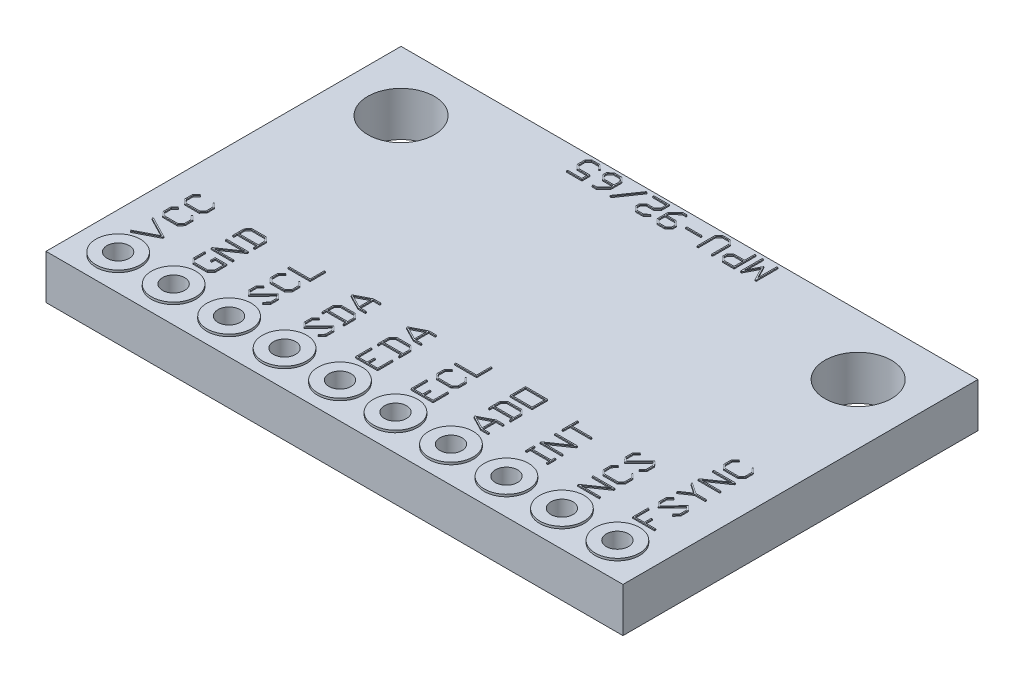
SolidWorks part; units mm, degrees
ref_plane "Alzado" through (0, 0, 0) normal (0, 0, 1) x (1, 0, 0)
ref_plane "Planta" through (0, 0, 0) normal (0, 1, 0) x (1, 0, 0)
ref_plane "Vista lateral" through (0, 0, 0) normal (1, 0, 0) x (0, 0, -1)
sketch "Croquis1" plane through (0, 0, 0) normal (0, 1, 0) x (1, 0, 0)
  line L1 (-13, -8) -> (13, -8)
  line L2 (-13, -8) -> (-13, 8)
  line L3 (-13, 8) -> (13, 8)
  line L4 (13, -8) -> (13, 8)
  line L5 (-13, -8) -> (13, 8) construction
  line L6 (-13, 8) -> (13, -8) construction
  circle A0 centre (-10.3, 5.3) radius 1.5
  circle A1 centre (10.3, 5.3) radius 1.5
  circle A2 centre (11.25, -6.5) radius 0.5
  circle A3 centre (11.25, -6.5) radius 1
  circle A4 centre (8.75, -6.5) radius 0.5
  circle A5 centre (8.75, -6.5) radius 1
  circle A6 centre (6.25, -6.5) radius 0.5
  circle A7 centre (6.25, -6.5) radius 1
  circle A8 centre (3.75, -6.5) radius 0.5
  circle A9 centre (3.75, -6.5) radius 1
  circle A10 centre (1.25, -6.5) radius 0.5
  circle A11 centre (1.25, -6.5) radius 1
  circle A12 centre (-1.25, -6.5) radius 0.5
  circle A13 centre (-1.25, -6.5) radius 1
  circle A14 centre (-3.75, -6.5) radius 0.5
  circle A15 centre (-3.75, -6.5) radius 1
  circle A16 centre (-6.25, -6.5) radius 0.5
  circle A17 centre (-6.25, -6.5) radius 1
  circle A18 centre (-8.75, -6.5) radius 0.5
  circle A19 centre (-8.75, -6.5) radius 1
  circle A20 centre (-11.25, -6.5) radius 0.5
  circle A21 centre (-11.25, -6.5) radius 1
  point P0 (0, 0)
  dimension "D3" = 2.7
  dimension "D7" = 1.5
  dimension "D1" = 26
  dimension "D2" = 16
  dimension "D4" = 2.7
  dimension "D5" = 2.7
  dimension "D6" = 2.7
  dimension "D8" = 1.75
  dimension "D9" = 10
extrude "Saliente-Extruir1" add sketch "Croquis1" against normal blind 2 contours L1 L4 L3 L2 A21 A19 A17 A15 A13 A11 A9 A7 A5 A3 A1 A0 | A3 | A5 | A7 | A9 | A11 | A13 | A15 | A17 | A19 | A21 region at (0, 0, -0.349)
extrude "Cortar-Extruir1" cut sketch "Croquis1<3>" against normal blind 2 contours A20 | A18 | A16 | A14 | A10 | A12 | A8 | A6 | A4 | A2
sketch "Croquis1<3>" plane through (0, 0, 0) normal (0, 1, 0) x (1, 0, 0) same geometry as "Croquis1"
extrude "Saliente-Extruir2" add sketch "Croquis1<4>" along normal blind 0.1 contours A19 A18 | A21 A20 | A17 A16 | A15 A14 | A13 A12 | A11 A10 | A9 A8 | A7 A6 | A5 A4 | A3 A2 region at (10.2783, 0, 6.5) region at (7.7783, 0, 6.5) region at (5.2783, 0, 6.5) region at (2.7783, 0, 6.5) region at (0.2783, 0, 6.5) region at (-2.2217, 0, 6.5) region at (-4.7217, 0, 6.5) region at (-7.2217, 0, 6.5) region at (-9.7217, 0, 6.5) region at (-12.2217, 0, 6.5)
sketch "Croquis1<4>" plane through (0, 0, 0) normal (0, 1, 0) x (1, 0, 0) same geometry as "Croquis1"
sketch "Croquis2" plane through (0, 0, 0) normal (0, 1, 0) x (1, 0, 0)
  line L0 (-10.8805, -5.5708) -> (-10.8805, -2.1435) construction
  line L1 (-8.3805, -5.5708) -> (-8.3805, -2.1435) construction
  line L2 (-5.8805, -5.5708) -> (-5.8805, -2.1435) construction
  line L3 (-3.3805, -5.5708) -> (-3.3805, -2.1435) construction
  line L4 (-0.8805, -5.5708) -> (-0.8805, -2.1435) construction
  line L5 (1.6195, -5.5708) -> (1.6195, -2.1435) construction
  line L6 (4.1195, -5.5708) -> (4.1195, -2.1435) construction
  line L7 (6.6195, -5.5708) -> (6.6195, -2.1435) construction
  line L8 (9.1195, -5.5708) -> (9.1195, -2.1435) construction
  line L9 (11.6195, -5.5708) -> (11.6195, -2.1435) construction
  line L10 (11.6195, -5.5708) -> (11.6195, -0.1979) construction
  circle A0 centre (-11.25, -6.5) radius 1 construction
  text T0 "VCC" font "Txt_IV25" height 1
  text T1 "GND" font "Txt_IV25" height 1
  text T2 "SCL"
  text T3 "SDA"
  text T4 "EDA"
  text T5 "ECL"
  text T6 "ADO"
  text T7 "INT"
  text T8 "NCS"
  text T9 "FSYNC"
  dimension "D1" = 10
extrude "Saliente-Extruir5" add sketch "Croquis2" along normal blind 0.05
sketch "Croquis6" plane through (0, 0, 0) normal (0, 1, 0) x (1, 0, 0)
  line L8 (12.8, -8) -> (12.8, 7.8)
  line L9 (12.8, 7.8) -> (-13, 7.8)
  line L10 (12.8, -8) -> (12.8, 7.8) construction
  line L11 (12.8, 7.8) -> (-13, 7.8) construction
  text T0 "MPU-92/65" font "Txt_IV25" height 1
  dimension "D1" = 0.2
extrude "Saliente-Extruir6" add sketch "Croquis6" along normal blind 0.05
ref_plane "Plano1" through (0, -1, 0) normal (0, -1, 0) x (-1, 0, 0)
mirror "Simetría1" about plane through (0, -1, 0) normal (0, -1, 0) of "Saliente-Extruir2"
